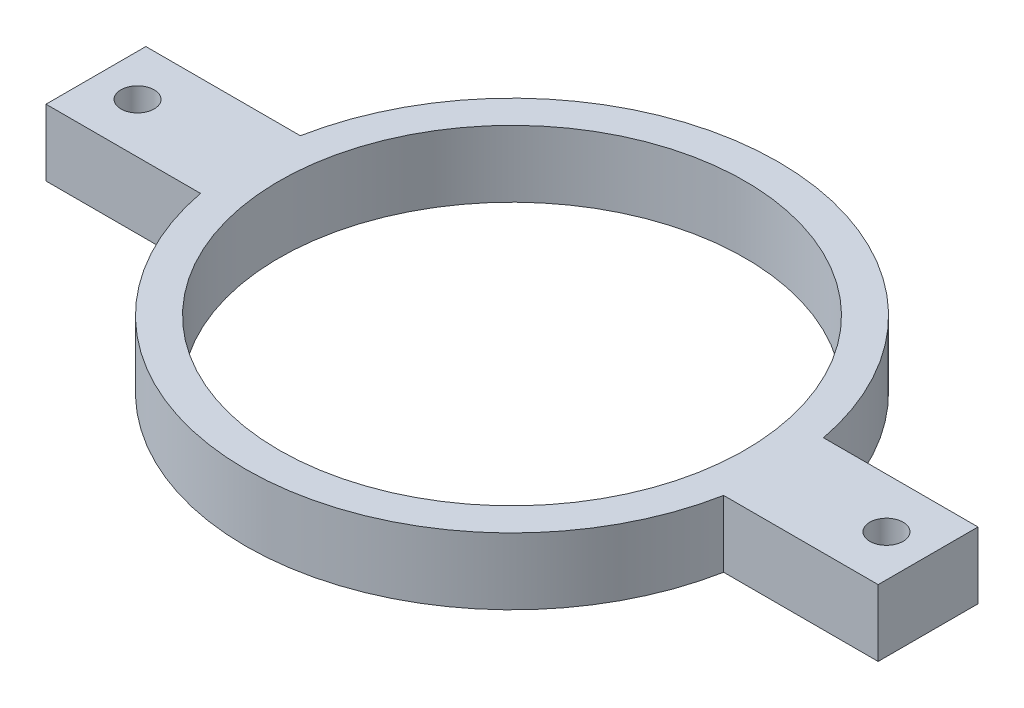
SolidWorks part; units mm, degrees
ref_plane "Front Plane" through (0, 0, 0) normal (0, 0, 1) x (1, 0, 0)
ref_plane "Top Plane" through (0, 0, 0) normal (0, 1, 0) x (1, 0, 0)
ref_plane "Right Plane" through (0, 0, 0) normal (1, 0, 0) x (0, 0, -1)
sketch "Sketch1" plane through (0, 0, 0) normal (0, 1, 0) x (1, 0, 0)
  line L1 (-12.5, -1.5) -> (12.5, -1.5)
  line L2 (-12.5, -1.5) -> (-12.5, 1.5)
  line L3 (-12.5, 1.5) -> (12.5, 1.5)
  line L4 (12.5, -1.5) -> (12.5, 1.5)
  circle A0 centre (0, 0) radius 8
  circle A1 centre (0, 0) radius 7
  circle A2 centre (-11.25, 0) radius 0.5
  circle A3 centre (11.25, 0) radius 0.5
  point P4 (0, 1.5)
  point P6 (-12.5, 0)
  point P14 (0, 0)
  dimension "D3" = 16
  dimension "D4" = 1
  dimension "D5" = 1
  dimension "D6" = 22.5
  dimension "D7" = 11.25
  dimension "D1" = 25
  dimension "D2" = 3
extrude "Boss-Extrude1" add sketch "Sketch1" along normal mid plane 2 contours A1 L1 A0 | A1 L1 A0 L3 | A0 L1 L4 L3 | A1 L3 A0 | A1 L3 A0 L1 | A0 L3 L2 L1 region at (-10.1637, 0, 0) region at (-7.4492, 0, 0) region at (-7.3478, 0, 1.6701) region at (0, 0, -7.8299) region at (10.1637, 0, 0) region at (7.4492, 0, 0)
sketch "Sketch4" plane through (0, 0, 0) normal (0, 0, 1) x (1, 0, 0)
  line L0 (-6.8767, 1.0074) -> (-6.4487, 1.95)
  line L1 (-6.4487, 1.95) -> (-6.0206, 1.0074)
  line L2 (-6.0206, 1.0074) -> (-6.0206, -0.9624)
  line L3 (-6.0206, -0.9624) -> (-6.8767, -0.9624)
  line L4 (-6.8767, -0.9624) -> (-6.8767, 1.0074)
  point P7 (-6.4487, -0.9624)
